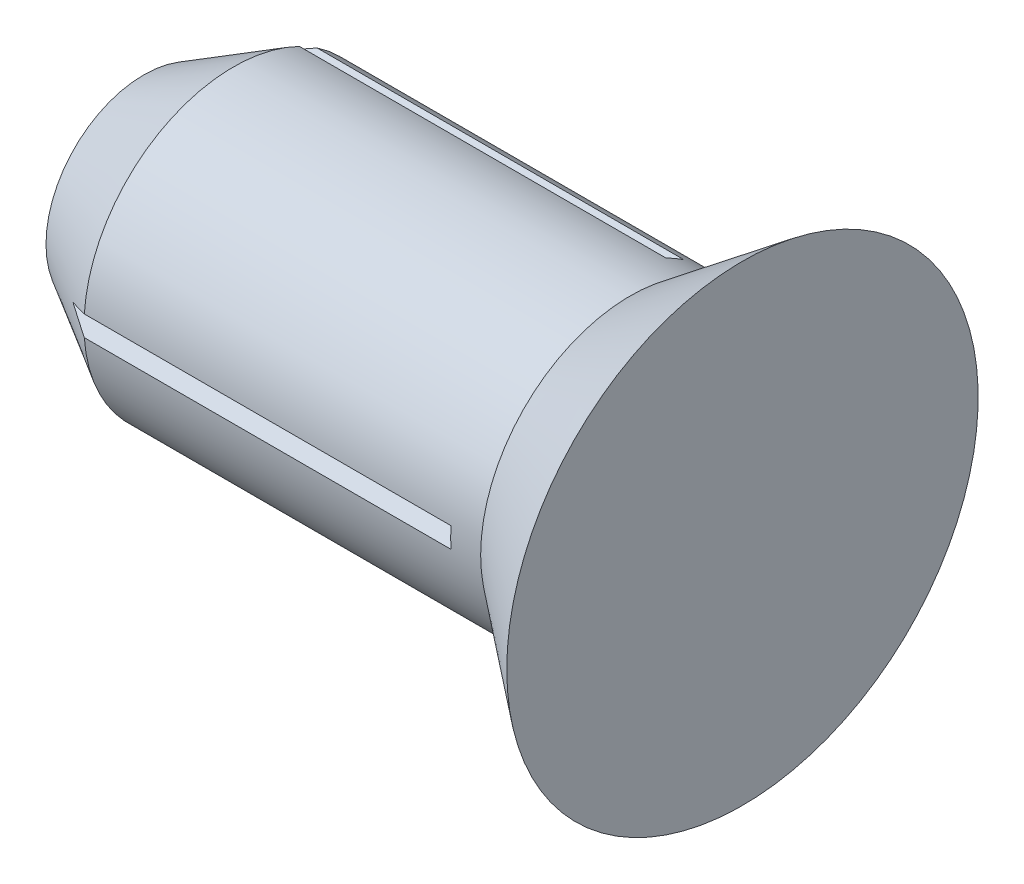
SolidWorks part; units mm, degrees
revolve "Base-Revolve" add sketch "Sketch1" angle 360 about L0
sketch "Sketch1" plane through (0, 0, 0) normal (0, 0, 1) x (1, 0, 0)
  line L0 (-40, 0) -> (40, 0) construction
  line L1 (-32.5065, 0) -> (-32.5065, 6.5359)
  line L2 (-26.5065, 10) -> (0, 10)
  line L3 (0, 10) -> (7.4935, 15.75)
  line L4 (7.4935, 15.75) -> (7.4935, 0)
  line L5 (0, -10) -> (7.4935, -15.75) construction
  line L6 (7.4935, 0) -> (-32.5065, 0)
  line L7 (-32.5065, 6.5359) -> (-26.5065, 10)
  dimension "D1" = 30
  dimension "HeadDia" = 31.5
  dimension "D2" = 75
  dimension "Diameter" = 20
  dimension "Length" = 40
  dimension "ChamferLength" = 6
ref_plane "Plane1" through (0, 0, 0) normal (0, 0, 1) x (1, 0, 0)
ref_plane "Plane2" through (0, 0, 0) normal (0, 1, 0) x (1, 0, 0)
ref_plane "Plane3" through (0, 0, 0) normal (1, 0, 0) x (0, 0, -1)
sketch "Sketch2" plane through (-32.5065, 0, 0) normal (-1, 0, 0) x (0, 0, 1)
  line L0 (0, 0) -> (12, 0) construction
  line L1 (9, 0) -> (10, 0.7002)
  line L2 (9, 0) -> (10, -0.7002)
  line L3 (10, -0.7002) -> (10, 0.7002)
  circle A0 centre (0, 0) radius 9 construction
  circle A1 centre (0, 0) radius 10 construction
  dimension "D1" = 18
  dimension "D2" = 70
  dimension "D3" = 35
extrude "Cut-Extrude1" cut sketch "Sketch2" against normal blind 30.5065
pattern_circular "CirPattern1" count 3 over 360 about axis through (-40, 0, 0) along (1, 0, 0) of "Cut-Extrude1"
equation "\"D1@Sketch2\" = \"Diameter@Sketch1\" * .9"
equation "\"D3@Sketch2\" = \"D2@Sketch2\" / 2"
equation "\"D1@Cut-Extrude1\" = \"Length@Sketch1\" - (((\"HeadDia@Sketch1\" - \"Diameter@Sketch1\") / 2.0) / tan((37.5 / 180) * 3.14159265)) - \"ChamferLength@Sketch1\" / 3"
